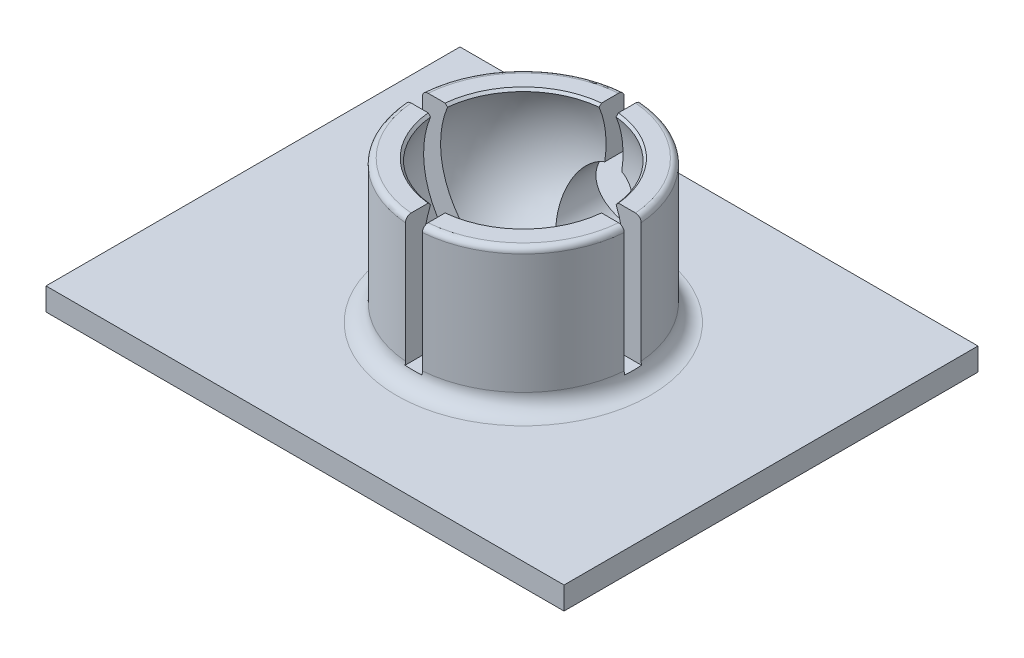
SolidWorks part; units mm, degrees
ref_plane "Front Plane" through (0, 0, 0) normal (0, 0, 1) x (1, 0, 0)
ref_plane "Top Plane" through (0, 0, 0) normal (0, 1, 0) x (1, 0, 0)
ref_plane "Right Plane" through (0, 0, 0) normal (1, 0, 0) x (0, 0, -1)
sketch "Sketch1" plane through (0, 0, 0) normal (0, 1, 0) x (1, 0, 0)
  line L0 (-23.9, 0) -> (21.9, 0) construction
  line L2 (-23.9, 18.3) -> (21.9, 18.3)
  line L3 (-23.9, 18.3) -> (-23.9, -18.3)
  line L4 (-23.9, -18.3) -> (21.9, -18.3)
  line L5 (21.9, 18.3) -> (21.9, -18.3)
  point P7 (21.9, 0)
  point P8 (-23.9, 0)
  dimension "D1" = 36.6
  dimension "D2" = 21.9
  dimension "D3" = 23.9
extrude "Boss-Extrude1" add sketch "Sketch1" along normal blind 2
sketch "Sketch2" plane through (0, 2, 0) normal (0, 1, 0) x (1, 0, 0)
  circle A0 centre (0, 0) radius 9.7
  dimension "D1" = 19.4
extrude "Boss-Extrude2" add sketch "Sketch2" along normal blind 12.5939
sketch "Sketch6" plane through (0, 0, 0) normal (0, 0, 1) x (1, 0, 0)
  line L0 (0, 0) -> (0, 19.4) construction
  line L2 (0, 19.4) -> (0, 3.2)
  line L3 (0, 3.2) -> (0, 19.4)
  arc A0 (0, 3.2) -> (0, 19.4) centre (0, 11.3) ccw
  dimension "D1" = 16.2
  dimension "D2" = 11.3
revolve "Cut-Revolve1" cut sketch "Sketch6" angle 360 about L3 region at (3.4377, 11.3, 0)
sketch "Sketch7" plane through (0, 0, 0) normal (0, 0, 1) x (1, 0, 0)
  circle A0 centre (0, 7.2) radius 2.85
  dimension "D1" = 5.7
  dimension "D2" = 7.2
extrude "Cut-Extrude2" cut sketch "Sketch7" against normal up to next
sketch "Sketch8" plane through (0, 14.5939, 0) normal (0, 1, 0) x (1, 0, 0)
  line L0 (10.7, 0.75) -> (-10.7, 0.75)
  line L1 (-0.75, 10.7) -> (0.75, 10.7)
  line L2 (-0.75, 10.7) -> (-0.75, -10.7)
  line L3 (-0.75, -10.7) -> (0.75, -10.7)
  line L4 (0.75, 10.7) -> (0.75, -10.7)
  line L5 (-0.75, 10.7) -> (0.75, -10.7) construction
  line L6 (-0.75, -10.7) -> (0.75, 10.7) construction
  line L7 (10.7, 0.75) -> (10.7, -0.75)
  line L8 (10.7, -0.75) -> (-10.7, -0.75)
  line L9 (-10.7, 0.75) -> (-10.7, -0.75)
  point P0 (0, 0)
  point P6 (0, 0)
  point P14 (0, 0)
  dimension "D1" = 1.5
  dimension "D2" = 21.4
extrude "Cut-Extrude4" cut sketch "Sketch8" against normal blind 11.3939 contours L0 L9 L8 L7 | L2 L1 L4 L3
fillet "Fillet1" radius 1.5 1 edges at (0, 2, 9.7)
chamfer "Chamfer1" distance 0.3 angle 45 4 edges at (-5.2326, 14.5939, -5.2326) (-5.2326, 14.5939, 5.2326) (5.2326, 14.5939, 5.2326) (5.2326, 14.5939, -5.2326) first distance on face at (-5.3395, 14.5939, -5.3395) first distance on face at (-5.3395, 14.5939, 5.3395) first distance on face at (5.3395, 14.5939, 5.3395) first distance on face at (5.3395, 14.5939, -5.3395)
fillet "Fillet2" radius 0.5 4 edges at (6.8589, 14.5939, 6.8589) (6.8589, 14.5939, -6.8589) (-6.8589, 14.5939, 6.8589) (-6.8589, 14.5939, -6.8589)
equation "\"board_w\"= 33.8"
equation "\"board_l\"= 41"
equation "\"stack_h\"= 19.5"
equation "\"module_w\"= 9.9"
equation "\"lens_d\"= 7.8"
equation "\"lens_from_end\"= 8"
equation "\"usb_w\"= 13"
equation "\"plug_h\"= 7"
equation "\"usb_from_back\"= 6"
equation "\"clear\"= 0.4"
equation "\"wall\"= 3"
equation "\"floor_t\"= 2.5"
equation "\"pocket_clear\"= 0.3"
equation "\"lens_clear\"= 0.6"
equation "\"plate_w\"= 16"
equation "\"plate_clear\"= 0.3"
equation "\"plate_t\"= 1.2"
equation "\"plate_seat\"= 0.8"
equation "\"window_d\"= 12"
equation "\"lid_t\"= 2"
equation "\"lid_gap\"= 1"
equation "\"groove_d\"= 1.2"
equation "\"groove_clear\"= 0.15"
equation "\"lip_top\"= 1.2"
equation "\"side_clear\"= 0.2"
equation "\"slide_clear\"= 0.2"
equation "\"ball_d\"= 16"
equation "\"ball_clear\"= 0.2"
equation "\"lip\"= 0.6"
equation "\"cup_floor\"= 1.2"
equation "\"slit_w\"= 1.5"
equation "\"slit_depth\"= \"cup_h\" - \"cup_floor\""
equation "\"lug_w\"= 16"
equation "\"m3_hole\"= 3.4"
equation "\"m3_nut\"= 5.7"
equation "\"m3_nut_d\"= 2.6"
equation "\"boss_d\"= 20"
equation "\"boss_h\"= 8"
equation "\"nut_af\"= 11.4"
equation "\"nut_t\"= 5.8"
equation "\"screw_hole\"= 6.6"
equation "\"in_l\"= \"board_l\" + 2 * \"clear\""
equation "\"in_w\"= \"board_w\" + 2 * \"clear\""
equation "\"out_l\"= \"in_l\" + 2 * \"wall\""
equation "\"out_w\"= \"in_w\" + 2 * \"wall\""
equation "\"y_groove\"= \"floor_t\" - \"plate_seat\" + \"stack_h\" + \"lid_gap\""
equation "\"groove_h\"= \"lid_t\" + 2 * \"groove_clear\""
equation "\"tray_h\"= \"y_groove\" + \"groove_h\" + \"lip_top\""
equation "\"lid_w\"= \"in_w\" + 2 * \"groove_d\" - 2 * \"side_clear\""
equation "\"lid_right\"= \"in_l\" / 2 + \"groove_d\" - \"slide_clear\""
equation "\"lid_left\"= \"out_l\" / 2"
equation "\"open_d\"= \"ball_d\" - 2 * \"lip\""
equation "\"c_ball\"= sqr( ( ( \"ball_d\" + \"ball_clear\" ) / 2 ) ^ 2 - ( \"open_d\" / 2 ) ^ 2 )"
equation "\"cup_h\"= \"cup_floor\" + ( \"ball_d\" + \"ball_clear\" ) / 2 + \"c_ball\""
equation "\"D2@Sketch1\"= \"lid_right\""
equation "\"D3@Sketch1\"=\"lid_left\""
equation "\"D1@Boss-Extrude1\"=\"lid_t\""
equation "\"D1@Sketch6\"=\"ball_d\"+\"ball_clear\""
equation "\"D2@Sketch6\"=\"lid_t\"+\"cup_h\"-\"c_ball\""
equation "\"lug_in\"= \"cup_d\" / 2 - 5"
equation "\"lug_out\"= \"cup_d\" / 2 + 4"
equation "\"finger_t\"= 1.6"
equation "\"cup_d\"= \"ball_d\" + \"ball_clear\" + 2 * \"finger_t\""
equation "\"D1@Sketch2\"=\"cup_d\""
equation "\"D1@Boss-Extrude2\"=\"cup_h\""
equation "\"D1@Sketch8\"=\"slit_w\""
equation "\"D1@Cut-Extrude4\"=\"slit_depth\""
equation "\"D1@Fillet1\"=1.5"
